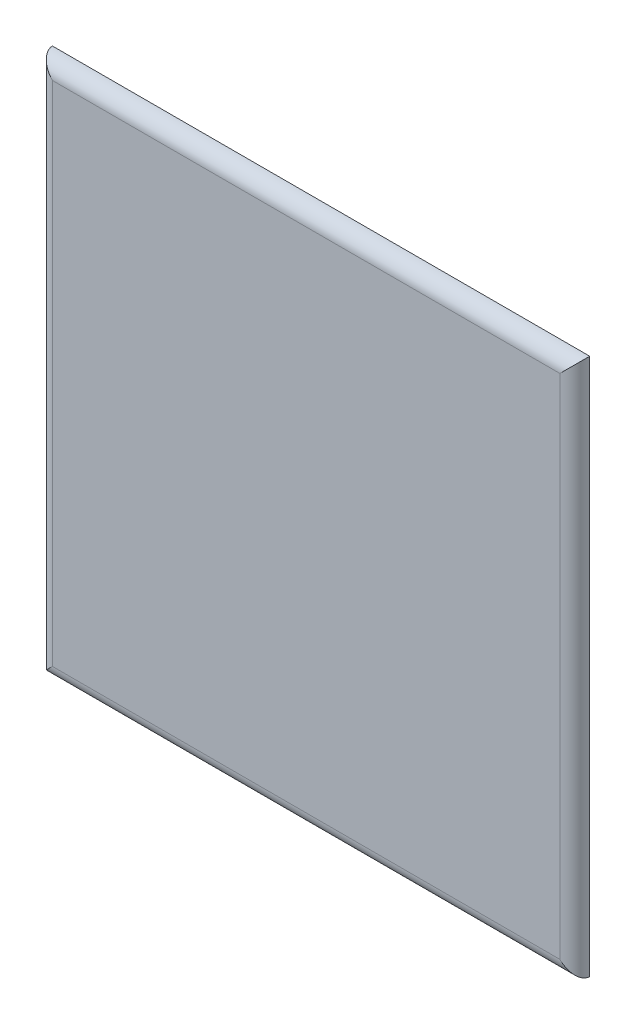
SolidWorks part; units mm, degrees
material "PS HI"
ref_plane "Ön Düzlem" through (0, 0, 0) normal (0, 0, 1) x (1, 0, 0)
ref_plane "Üst Düzlem" through (0, 0, 0) normal (0, 1, 0) x (1, 0, 0)
ref_plane "Sağ Düzlem" through (0, 0, 0) normal (1, 0, 0) x (0, 0, -1)
sketch "Çizim1" plane through (0, 0, 0) normal (0, 0, 1) x (1, 0, 0)
  line L1 (-9, -9) -> (9, -9)
  line L2 (-9, -9) -> (-9, 9)
  line L3 (-9, 9) -> (9, 9)
  line L4 (9, -9) -> (9, 9)
  line L5 (-9, -9) -> (9, 9) construction
  line L6 (-9, 9) -> (9, -9) construction
  point P0 (0, 0)
  dimension "D1" = 18
  dimension "D2" = 18
extrude "Yükseklik-Ekstrüzyon1" add sketch "Çizim1" along normal mid plane 0.5
fillet "Radyus1" radius 0.5 4 edges at (9, 0, 0.25) (0, 9, 0.25) (-9, 0, 0.25) (0, -9, 0.25)
